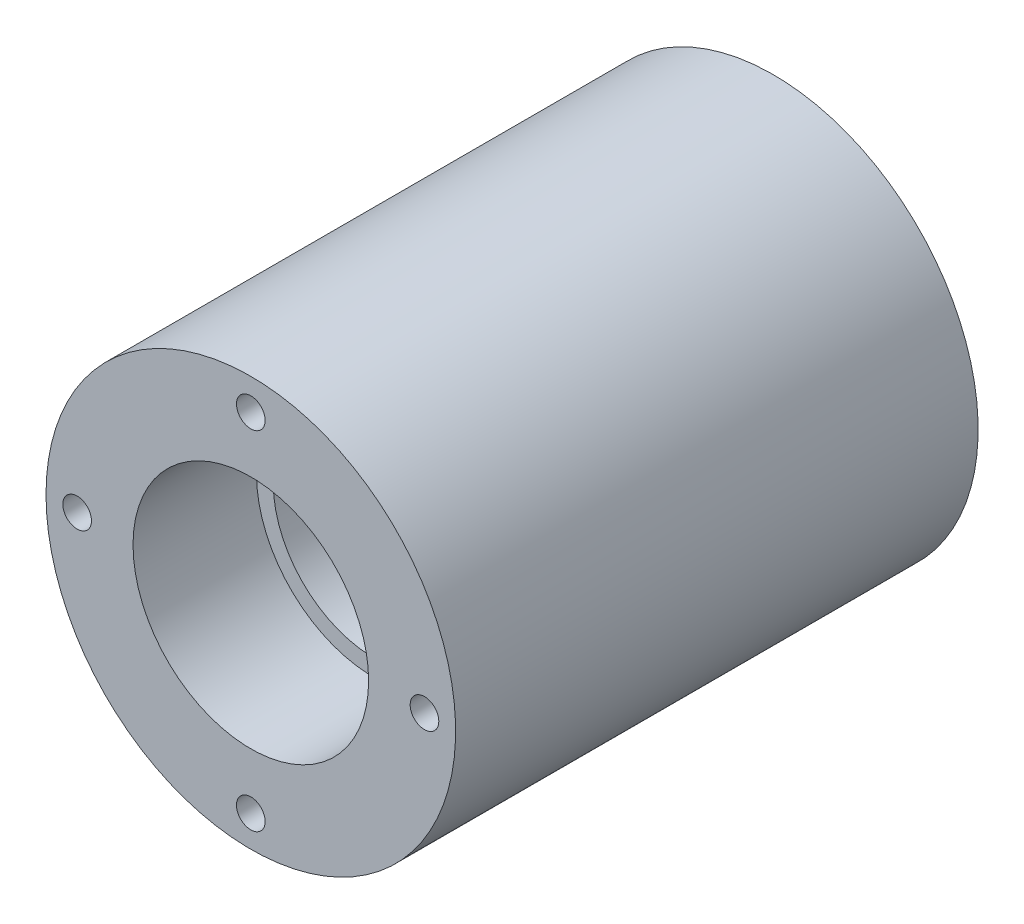
SolidWorks part; units mm, degrees
material "6061-T6 (SS)"
ref_plane "Front Plane" through (0, 0, 0) normal (0, 0, 1) x (1, 0, 0)
ref_plane "Top Plane" through (0, 0, 0) normal (0, 1, 0) x (1, 0, 0)
ref_plane "Right Plane" through (0, 0, 0) normal (1, 0, 0) x (0, 0, -1)
sketch "Shaft Sketch" plane through (0, 0, 0) normal (1, 0, 0) x (0, 0, -1)
  line L0 (141.5523, 0) -> (-87.5573, 0)
  line L1 (93.1469, 36.5125) -> (0, 36.5125) construction
  line L2 (93.1469, 36.5125) -> (93.1469, -36.5125) construction
  line L3 (93.1469, -36.5125) -> (0, -36.5125) construction
  line L4 (0, 36.5125) -> (0, -36.5125) construction
  line L5 (0, 36.5125) -> (-15.24, 36.5125) construction
  line L6 (0, 36.5125) -> (0, -36.5125) construction
  line L7 (0, -36.5125) -> (-15.24, -36.5125) construction
  line L8 (-15.24, 36.5125) -> (-15.24, -36.5125) construction
  line L9 (-22.86, 9.525) -> (0, 9.525)
  line L10 (-22.86, 9.525) -> (-22.86, -9.525)
  line L11 (-22.86, -9.525) -> (0, -9.525)
  line L12 (0, 9.525) -> (0, -9.525)
  line L13 (22, 10.0076) -> (10, 10.0076)
  line L14 (22, 10.0076) -> (22, -10.0076)
  line L15 (22, -10.0076) -> (10, -10.0076)
  line L16 (10, 10.0076) -> (10, -10.0076)
  line L17 (64.5719, 9.9949) -> (52.5719, 9.9949)
  line L18 (64.5719, 9.9949) -> (64.5719, -9.9949)
  line L19 (64.5719, -9.9949) -> (52.5719, -9.9949)
  line L20 (52.5719, 9.9949) -> (52.5719, -9.9949)
  line L22 (52.5719, 9.9949) -> (22, 9.9949)
  line L23 (52.5719, 9.9949) -> (52.5719, -9.9949)
  line L24 (52.5719, -9.9949) -> (22, -9.9949)
  line L25 (22, 9.9949) -> (22, -9.9949)
  line L26 (64.5719, 9.525) -> (89.9719, 9.525)
  line L27 (64.5719, 9.525) -> (64.5719, -9.525)
  line L28 (64.5719, -9.525) -> (89.9719, -9.525)
  line L29 (89.9719, 9.525) -> (89.9719, -9.525)
  line L30 (115.1417, 7.9375) -> (130.0369, 7.9375)
  line L31 (115.1417, 7.9375) -> (115.1417, -7.9375)
  line L32 (115.1417, -7.9375) -> (130.0369, -7.9375)
  line L33 (130.0369, 7.9375) -> (130.0369, -7.9375)
  line L34 (10, 12.5) -> (0, 12.5)
  line L35 (10, 12.5) -> (10, -12.5)
  line L36 (10, -12.5) -> (0, -12.5)
  line L37 (0, 12.5) -> (0, -12.5)
  line L38 (-41.86, 7.0002) -> (-26.86, 7.0002)
  line L39 (-41.86, 7.0002) -> (-41.86, -7.0002)
  line L40 (-41.86, -7.0002) -> (-26.86, -7.0002)
  line L41 (-26.86, 7.0002) -> (-26.86, -7.0002)
  line L42 (93.1469, 36.5125) -> (102.0369, 36.5125) construction
  line L43 (93.1469, 36.5125) -> (93.1469, -36.5125) construction
  line L44 (93.1469, -36.5125) -> (102.0369, -36.5125) construction
  line L45 (102.0369, 36.5125) -> (102.0369, -36.5125) construction
  line L46 (115.1417, -7.9375) -> (89.9719, -7.9375)
  line L47 (115.1417, -7.9375) -> (115.1417, 7.9375)
  line L48 (115.1417, 7.9375) -> (89.9719, 7.9375)
  line L49 (89.9719, -7.9375) -> (89.9719, 7.9375)
  line L54 (-22.86, 7.5) -> (-26.86, 7.5)
  line L55 (-22.86, 7.5) -> (-22.86, -7.5)
  line L56 (-22.86, -7.5) -> (-26.86, -7.5)
  line L57 (-26.86, 7.5) -> (-26.86, -7.5)
sketch "Housing Sketch" plane through (0, 0, 0) normal (1, 0, 0) x (0, 0, -1)
  line L0 (64.5719, 9.9949) -> (64.5719, -9.9949) construction
  line L1 (52.5719, 9.9949) -> (52.5719, -9.9949) construction
  line L2 (22, 10.0076) -> (22, -10.0076) construction
  line L3 (10, 10.0076) -> (10, -10.0076) construction
  line L4 (0, 36.5125) -> (0, -36.5125) construction
  line L5 (93.1469, 36.5125) -> (0, 36.5125) construction
  line L6 (93.1469, 36.5125) -> (93.1469, -36.5125) construction
  line L7 (64.5719, 9.9949) -> (64.5719, -9.9949)
  line L8 (52.5719, 9.9949) -> (52.5719, -9.9949)
  line L9 (22, 10.0076) -> (22, -10.0076)
  line L10 (10, 10.0076) -> (10, -10.0076)
  line L11 (0, 36.5125) -> (0, -36.5125)
  line L12 (93.1469, 36.5125) -> (0, 36.5125)
  line L13 (93.1469, 36.5125) -> (93.1469, -36.5125)
  line L15 (-999.0031, 0) -> (48976.0676, 0)
  line L17 (93.1469, 21) -> (52.5719, 21)
  line L18 (52.5719, 21) -> (52.5719, 18)
  line L19 (52.5719, 18) -> (22, 18)
  line L20 (22, 18) -> (22, 21)
  line L21 (22, 21) -> (0, 21)
  dimension "D1" = 21
  dimension "D2" = 3
revolve "Housing Revolve" add sketch "Housing Sketch" angle 360 about L0 region at (0, 28.2038, -46.0191)
ref_plane "Center Plane" through (0, 0, -46.5734) normal (0, 0, -1) x (-1, 0, 0)
sketch "Bolt Location" plane through (0, 0, 0) normal (0, 0, 1) x (1, 0, 0)
  circle A0 centre (0, 0) radius 30.9575 construction
  point P3 (0, 30.9575)
  point P4 (30.9575, 0)
  point P5 (0, -30.9575)
  point P6 (-30.9575, 0)
  point P7 (-47.0885, 17.8863)
  dimension "D1" = 61.915
hole_wizard "Tap Drill for 1/4-20 Tap2" positions "Sketch6" profile "Sketch8" hole size "1/4-20" standard "ANSI Inch"
sketch "Sketch6" plane through (0, 0, 0) normal (0, 0, 1) x (1, 0, 0)
  point P0 (0, 30.9575)
  point P3 (30.9575, 0)
  point P6 (0, -30.9575)
  point P9 (-30.9575, 0)
sketch "Sketch8" plane through (0, 30.9575, 0) normal (1, 0, 0) x (0, -1, 0)
  line L0 (0, 0) -> (0, 14.2338)
  line L1 (0, 14.2338) -> (2.5527, 12.7)
  line L2 (2.5527, 12.7) -> (2.5527, 0)
  line L5 (2.5527, 0) -> (0, 0)
  line L10 (0, 14.2338) -> (-2.5527, 12.7) construction
  line L11 (0, -6.35) -> (0, 107.95) construction
  dimension "Hole Dia." = 5.1054
  dimension "Hole Depth" = 12.7
  dimension "Drill Angle" = 118
mirror "Mirror1" about plane through (0, 0, -46.5734) normal (0, 0, -1) of "Tap Drill for 1/4-20 Tap2"
